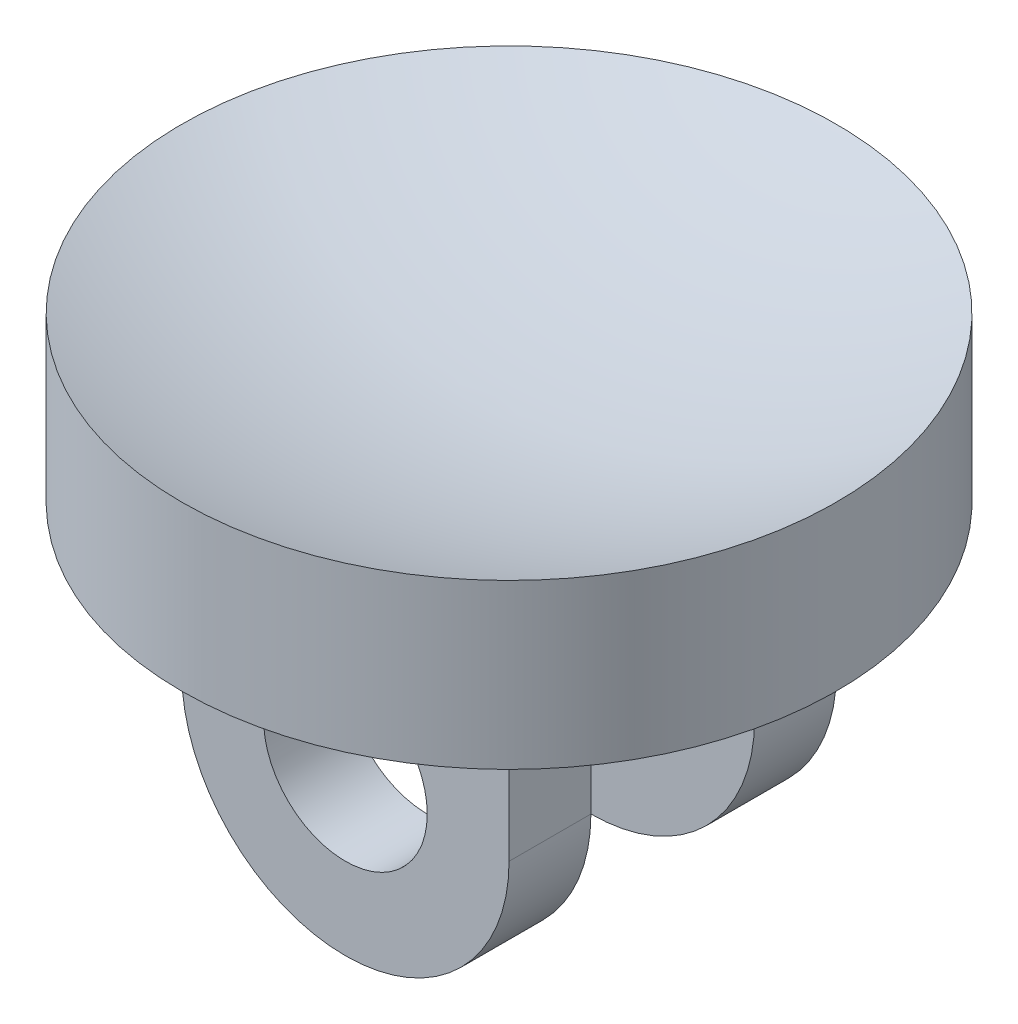
SolidWorks part; units mm, degrees
ref_plane "Front Plane" through (0, 0, 0) normal (0, 0, 1) x (1, 0, 0)
ref_plane "Top Plane" through (0, 0, 0) normal (0, 1, 0) x (1, 0, 0)
ref_plane "Right Plane" through (0, 0, 0) normal (1, 0, 0) x (0, 0, -1)
sketch "Sketch1" plane through (0, 0, 0) normal (0, 1, 0) x (1, 0, 0)
  circle A0 centre (0, 0) radius 12.7
  dimension "D1" = 25.4
extrude "Boss-Extrude1" add sketch "Sketch1" along normal blind 6.35
dome "Dome1" faces to dome 1 distance 2.54 reverse direction yes elliptical dome no face at (0, 6.35, 12.7) parameters "D1"=2.54
ref_plane "Plane1" through (0, 0, 3.175) normal (0, 0, 1) x (1, 0, 0)
sketch "Sketch2" plane through (0, 0, 3.175) normal (0, 0, 1) x (1, 0, 0)
  line L0 (-6.35, 0) -> (6.35, 0)
  line L1 (-12.7, 0) -> (12.7, 0) construction
  line L2 (-6.35, 0) -> (-6.35, -5.715)
  line L3 (6.35, 0) -> (6.35, -5.715)
  arc A0 (-6.35, -5.715) -> (6.35, -5.715) centre (0, -5.715) ccw
  circle A1 centre (0, -5.715) radius 3.175
  point P4 (0, 0)
  point P9 (0, 0)
  point P11 (0, -5.2396)
  point P12 (0, -6.1177)
  dimension "D3" = 3.175
  dimension "D1" = 6.35
  dimension "D2" = 2.54
extrude "Boss-Extrude2" add sketch "Sketch2" along normal blind 3.175
mirror "Mirror1" about plane through (0, 0, 0) normal (0, 0, 1) of "Boss-Extrude2"
